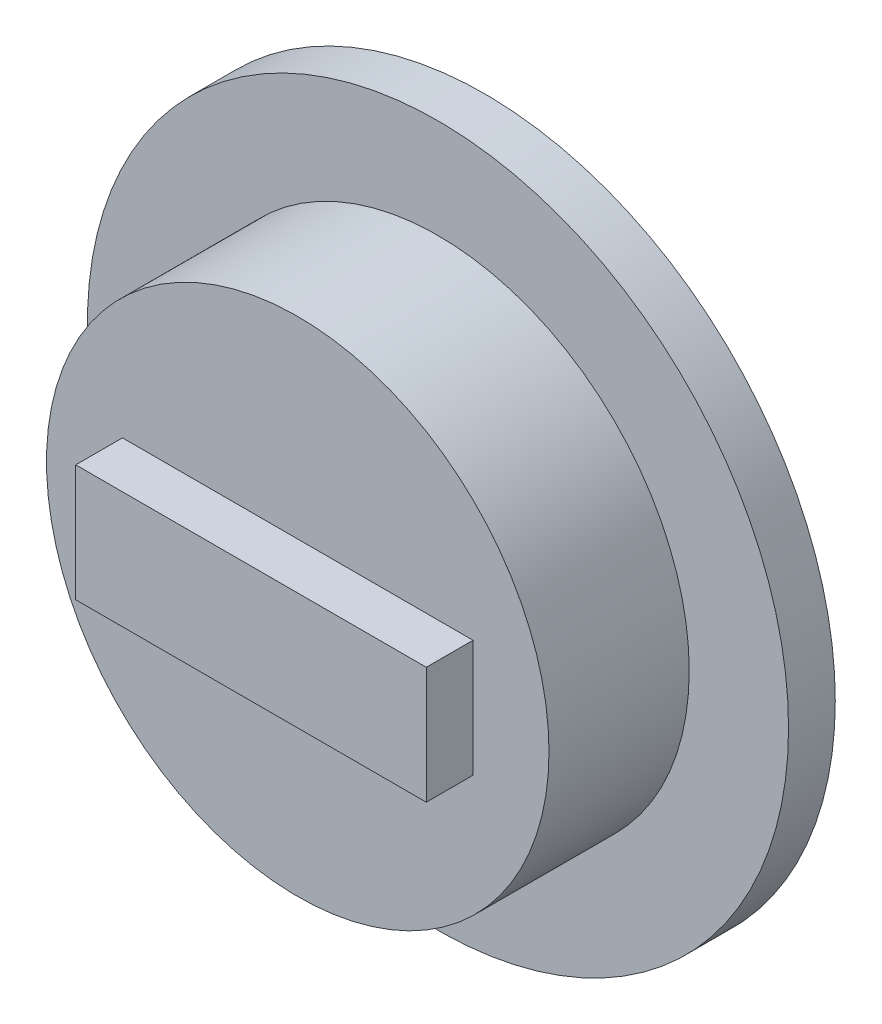
SolidWorks part; units mm, degrees
ref_plane "Спереди" through (0, 0, 0) normal (0, 0, 1) x (1, 0, 0)
ref_plane "Сверху" through (0, 0, 0) normal (0, 1, 0) x (1, 0, 0)
ref_plane "Справа" through (0, 0, 0) normal (1, 0, 0) x (0, 0, -1)
sketch "Эскиз1" plane through (0, 0, 0) normal (0, 0, 1) x (1, 0, 0)
  circle A0 centre (0, 0) radius 15
  dimension "D1" = 30
extrude "Бобышка-Вытянуть1" add sketch "Эскиз1" along normal blind 2
sketch "Эскиз2" plane through (0, 0, 0) normal (0, 0, 1) x (1, 0, 0)
  circle A0 centre (0, 0) radius 10.75
  dimension "D1" = 21.5
extrude "Бобышка-Вытянуть2" add sketch "Эскиз2" along normal blind 6 from offset 2
sketch "Эскиз3" plane through (0, 0, 0) normal (0, 0, 1) x (1, 0, 0)
  line L1 (-7.5, -2.5) -> (7.5, -2.5)
  line L2 (-7.5, -2.5) -> (-7.5, 2.5)
  line L3 (-7.5, 2.5) -> (7.5, 2.5)
  line L4 (7.5, -2.5) -> (7.5, 2.5)
  line L5 (-7.5, -2.5) -> (7.5, 2.5) construction
  line L6 (-7.5, 2.5) -> (7.5, -2.5) construction
  point P0 (0, 0)
  dimension "D1" = 5
  dimension "D2" = 15
extrude "Бобышка-Вытянуть3" add sketch "Эскиз3" along normal blind 10
sketch "Эскиз4" plane through (0, 0, 0) normal (0, 0, 1) x (1, 0, 0)
  line L1 (-7.5, 2) -> (7.5, 2)
  line L2 (-7.5, 2) -> (-7.5, 6)
  line L3 (-7.5, 6) -> (7.5, 6)
  line L4 (7.5, 2) -> (7.5, 6)
  line L5 (-7.5, -6) -> (7.5, -6)
  line L6 (-7.5, -6) -> (-7.5, -2)
  line L7 (-7.5, -2) -> (7.5, -2)
  line L8 (7.5, -6) -> (7.5, -2)
  dimension "D1" = 15
  dimension "D2" = 7.5
  dimension "D3" = 2
  dimension "D4" = 4
  dimension "D5" = 4
  dimension "D6" = 7.5
  dimension "D7" = 15
  dimension "D8" = 2
extrude "Вырез-Вытянуть1" cut sketch "Эскиз4" along normal blind 4
